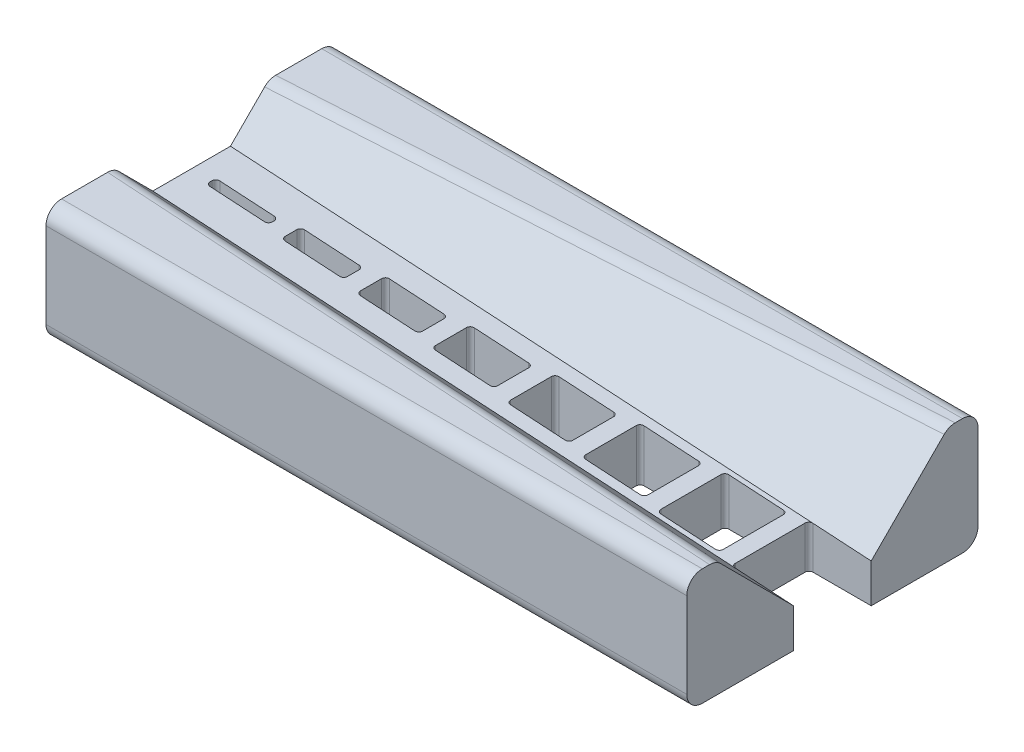
SolidWorks part; units mm, degrees
material "201 Annealed Stainless Steel (SS)"
ref_plane "Front Plane" through (0, 0, 0) normal (0, 0, 1) x (1, 0, 0)
ref_plane "Top Plane" through (0, 0, 0) normal (0, 1, 0) x (1, 0, 0)
ref_plane "Right Plane" through (0, 0, 0) normal (1, 0, 0) x (0, 0, -1)
sketch "Sketch1" plane through (0, 0, 0) normal (0, 0, 1) x (1, 0, 0)
  line L0 (-105.824, 0) -> (103.726, 0)
  line L1 (103.726, 0) -> (103.726, 12.7)
  line L2 (103.726, 12.7) -> (-105.824, 25.4)
  line L3 (-105.824, 25.4) -> (-105.824, 0)
  dimension "D1" = 209.55
  dimension "D2" = 12.7
  dimension "D3" = 25.4
  dimension "D4" = 103.726
extrude "Boss-Extrude1" add sketch "Sketch1" along normal mid plane 76.2
sketch "Sketch2" plane through (0, 0, -38.1) normal (0, 0, -1) x (-1, 0, 0)
  line L0 (-103.726, 0) -> (-103.726, 38.1)
  line L1 (-103.726, 38.1) -> (105.824, 38.1)
  line L2 (105.824, 38.1) -> (105.824, 0)
  line L3 (105.824, 0) -> (-103.726, 0)
  dimension "D1" = 38.1
extrude "Boss-Extrude2" add sketch "Sketch2" along normal blind 9.525 contours L1 L2 L3 L0
mirror "Mirror1" about plane through (0, 0, 0) normal (0, 0, 1) of "Boss-Extrude2"
sketch "Sketch3" plane through (0, 0, 0) normal (0, -1, 0) x (1, 0, 0)
  line L0 (-99.474, 1.5875) -> (-99.474, -1.5875)
  line L1 (-99.474, -1.5875) -> (-79.154, -1.5875)
  line L2 (-79.154, -1.5875) -> (-79.154, 1.5875)
  line L3 (-79.154, 1.5875) -> (-99.474, 1.5875)
  line L4 (103.726, 0) -> (-105.824, 0) construction
  line L5 (103.726, 47.625) -> (103.726, -47.625) construction
  line L6 (-52.992, 3.175) -> (-73.312, 3.175)
  line L7 (-73.312, 3.175) -> (-73.312, -3.175)
  line L8 (-73.312, -3.175) -> (-52.992, -3.175)
  line L9 (-52.992, -3.175) -> (-52.992, 3.175)
  line L10 (-26.83, 4.7625) -> (-47.15, 4.7625)
  line L11 (-47.15, 4.7625) -> (-47.15, -4.7625)
  line L12 (-47.15, -4.7625) -> (-26.83, -4.7625)
  line L13 (-26.83, -4.7625) -> (-26.83, 4.7625)
  line L14 (-0.668, 6.35) -> (-20.988, 6.35)
  line L15 (-20.988, 6.35) -> (-20.988, -6.35)
  line L16 (-20.988, -6.35) -> (-0.668, -6.35)
  line L17 (-0.668, -6.35) -> (-0.668, 6.35)
  line L18 (25.494, 7.9375) -> (5.174, 7.9375)
  line L19 (5.174, 7.9375) -> (5.174, -7.9375)
  line L20 (5.174, -7.9375) -> (25.494, -7.9375)
  line L21 (25.494, -7.9375) -> (25.494, 7.9375)
  line L22 (51.656, 9.525) -> (31.336, 9.525)
  line L23 (31.336, 9.525) -> (31.336, -9.525)
  line L24 (31.336, -9.525) -> (51.656, -9.525)
  line L25 (51.656, -9.525) -> (51.656, 9.525)
  line L26 (77.818, 11.1125) -> (57.498, 11.1125)
  line L27 (57.498, 11.1125) -> (57.498, -11.1125)
  line L28 (57.498, -11.1125) -> (77.818, -11.1125)
  line L29 (77.818, -11.1125) -> (77.818, 11.1125)
  line L30 (103.726, 12.7) -> (83.406, 12.7)
  line L31 (83.406, 12.7) -> (83.406, -12.7)
  line L32 (83.406, -12.7) -> (103.726, -12.7)
  line L33 (103.726, -12.7) -> (103.726, 12.7)
  line L34 (-105.824, 47.625) -> (-105.824, -47.625) construction
  point P2 (103.726, 0)
  point P7 (77.818, 0)
  point P9 (57.498, 0)
  point P38 (51.656, 0)
  point P39 (31.336, 0)
  point P40 (25.494, 0)
  point P44 (-79.154, 0)
  point P45 (-52.992, 0)
  point P46 (-26.83, 0)
  point P47 (-0.668, 0)
  dimension "D1" = 25.4
  dimension "D2" = 22.225
  dimension "D3" = 19.05
  dimension "D4" = 15.875
  dimension "D6" = 9.525
  dimension "D5" = 12.7
  dimension "D7" = 6.35
  dimension "D8" = 3.175
  dimension "D9" = 6.35
  dimension "D10" = 26.67
  dimension "D11" = 32.512
  dimension "D12" = 58.674
  dimension "D13" = 84.836
  dimension "D14" = 110.998
  dimension "D15" = 137.16
  dimension "D16" = 163.322
extrude "Cut-Extrude1" cut sketch "Sketch3" against normal through all
chamfer "Chamfer1" distance 25.4 angle 45 1 edges at (-1.049, 19.05, 38.1)
chamfer "Chamfer2" distance 25.4 angle 45 1 edges at (-1.049, 19.05, -38.1)
fillet "Fillet1" radius 1.27 30 edges at (77.818, 7.1351, -11.1125) (51.656, 7.9279, -9.525) (25.494, 8.7207, -7.9375) (-0.668, 9.5135, -6.35) (-26.83, 10.3062, -4.7625) (-52.992, 11.099, -3.175) (-79.154, 11.8918, -1.5875) (-79.154, 11.8918, 1.5875) (-52.992, 11.099, 3.175) (-26.83, 10.3062, 4.7625) (-0.668, 9.5135, 6.35) (25.494, 8.7207, 7.9375) (51.656, 7.9279, 9.525) (77.818, 7.1351, 11.1125) (83.406, 6.9658, -12.7) (57.498, 7.7508, -11.1125) (31.336, 8.5436, -9.525) (5.174, 9.3364, -7.9375) (-20.988, 10.1292, -6.35) (-47.15, 10.922, -4.7625) (-73.312, 11.7148, -3.175) (-99.474, 12.5076, -1.5875) (-99.474, 12.5076, 1.5875) (-73.312, 11.7148, 3.175) (-47.15, 10.922, 4.7625) (-20.988, 10.1292, 6.35) (5.174, 9.3364, 7.9375) (31.336, 8.5436, 9.525) (57.498, 7.7508, 11.1125) (83.406, 6.9658, 12.7)
fillet "Fillet2" radius 5.08 6 edges at (-1.049, 0, -47.625) (-1.049, 0, 47.625) (-1.049, 38.1, 47.625) (-1.049, 38.1, 31.7151) (-1.049, 38.1, -31.7151) (-1.049, 38.1, -47.625)
